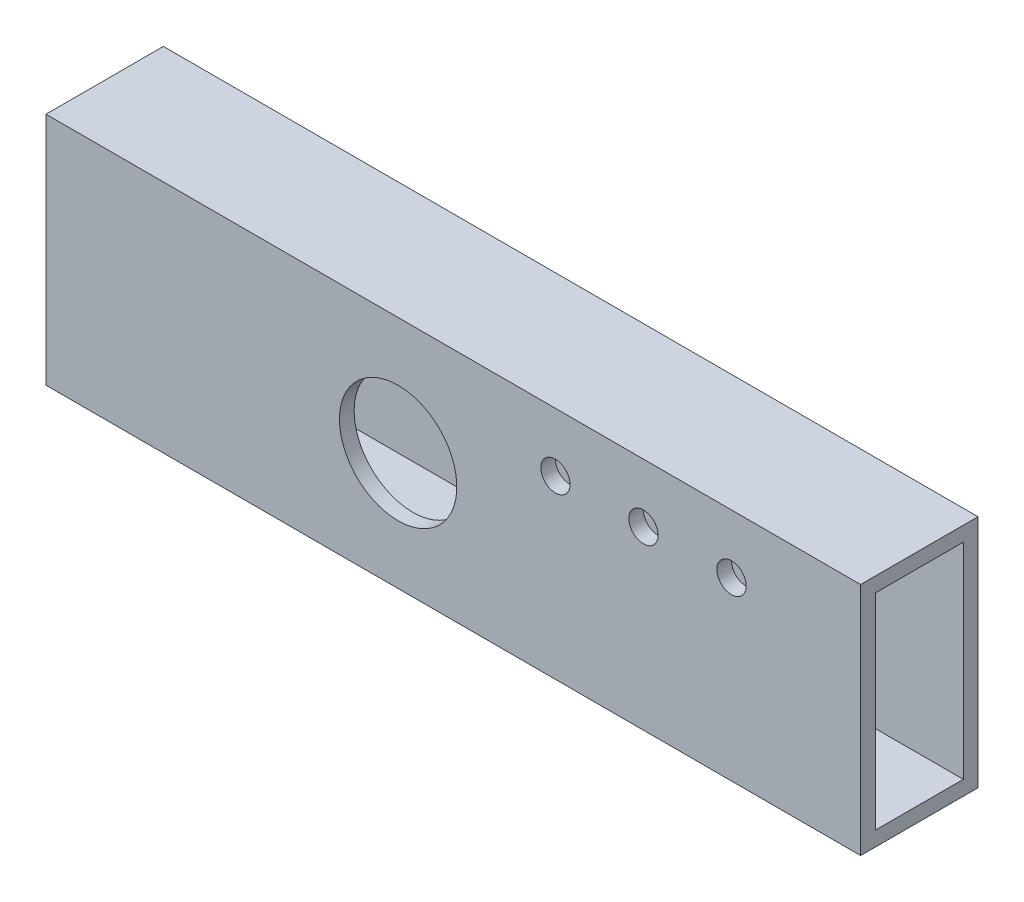
SolidWorks part; units mm, degrees
ref_plane "Front Plane" through (0, 0, 0) normal (0, 0, 1) x (1, 0, 0)
ref_plane "Top Plane" through (0, 0, 0) normal (0, 1, 0) x (1, 0, 0)
ref_plane "Right Plane" through (0, 0, 0) normal (1, 0, 0) x (0, 0, -1)
sketch "Sketch1" plane through (0, 0, 0) normal (0, 1, 0) x (1, 0, 0)
  line L1 (0, 0) -> (176.276, 0)
  line L2 (0, 0) -> (0, 25.4)
  line L3 (0, 25.4) -> (176.276, 25.4)
  line L4 (176.276, 0) -> (176.276, 25.4)
  dimension "D1" = 176.276
  dimension "D2" = 25.4
extrude "Boss-Extrude1" add sketch "Sketch1" along normal blind 50.8
sketch "Sketch2" plane through (176.276, 0, 0) normal (1, 0, 0) x (0, 0, -1)
  line L0 (3.175, 47.625) -> (3.175, 3.175)
  line L1 (0, 50.8) -> (25.4, 50.8)
  line L2 (0, 50.8) -> (0, 0)
  line L3 (0, 0) -> (25.4, 0)
  line L4 (25.4, 50.8) -> (25.4, 0)
  line L5 (3.175, 3.175) -> (22.225, 3.175)
  line L6 (22.225, 47.625) -> (22.225, 3.175)
  line L7 (3.175, 47.625) -> (22.225, 47.625)
  dimension "D1" = 3.175
extrude "Cut-Extrude1" cut sketch "Sketch2" against normal through all flip side to cut
sketch "Sketch3" plane through (0, 0, -25.4) normal (0, 0, -1) x (-1, 0, 0)
  line L1 (-176.276, 50.8) -> (0, 50.8) construction
  line L2 (0, 50.8) -> (0, 0) construction
  circle A0 centre (-76.2, 25.4) radius 12.7
  dimension "D1" = 25.4
  dimension "D4" = 76.2
  dimension "D3" = 25.4
extrude "Cut-Extrude2" cut sketch "Sketch3" against normal through all
sketch "Sketch4" plane through (0, 0, 0) normal (0, 0, 1) x (1, 0, 0)
  line L0 (176.276, 50.8) -> (176.276, 0) construction
  line L2 (0, 50.8) -> (176.276, 50.8) construction
  circle A0 centre (148.336, 38.1) radius 3.175
  circle A1 centre (129.286, 38.1) radius 3.175
  circle A2 centre (110.236, 38.1) radius 3.175
  dimension "D1" = 6.35
  dimension "D2" = 6.35
  dimension "D3" = 6.35
  dimension "D4" = 27.94
  dimension "D5" = 19.05
  dimension "D6" = 19.05
  dimension "D7" = 12.7
  dimension "D8" = 12.7
  dimension "D9" = 12.7
extrude "Cut-Extrude3" cut sketch "Sketch4" against normal through all
